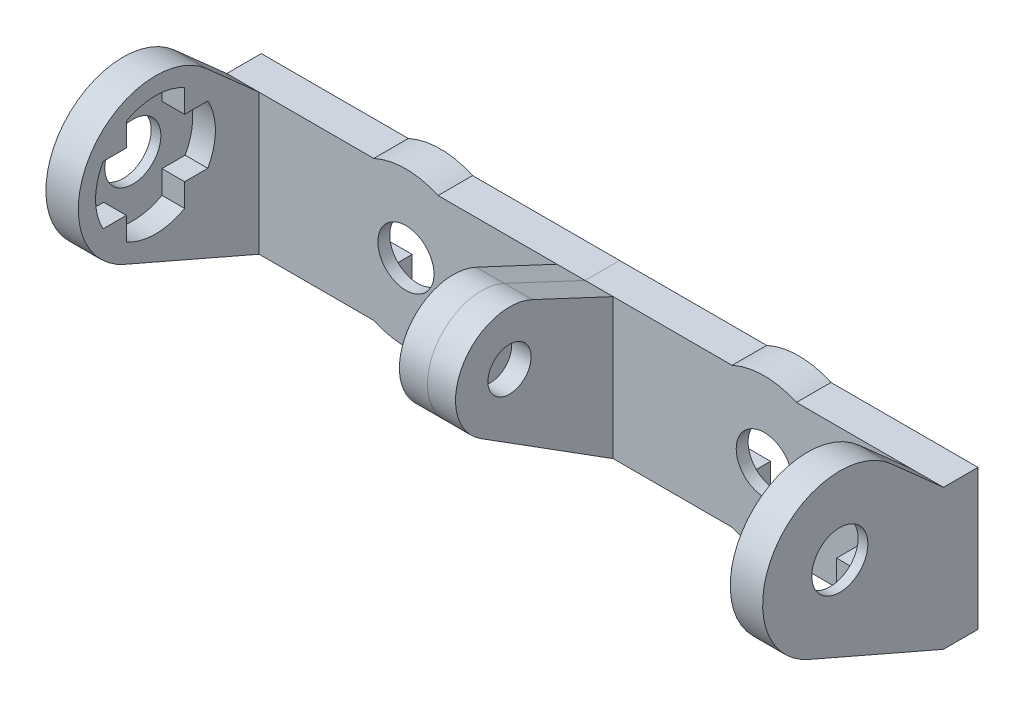
SolidWorks part; units mm, degrees
ref_plane "正面" through (0, 0, 0) normal (0, 0, 1) x (1, 0, 0)
ref_plane "平面" through (0, 0, 0) normal (0, 1, 0) x (1, 0, 0)
ref_plane "右側面" through (0, 0, 0) normal (1, 0, 0) x (0, 0, -1)
sketch "ｽｹｯﾁ1" plane through (0, 0, 0) normal (0, 0, 1) x (1, 0, 0)
  line L0 (0, 0) -> (13.6216, 0)
  line L1 (33.2, 0) -> (33.2, 13.0002)
  line L2 (33.2, 13.0002) -> (19.5784, 13.0002)
  line L3 (0, 13.0002) -> (0, 0)
  line L4 (16.6, 13.0002) -> (16.6, 0) construction
  line L5 (16.6, 6.5001) -> (33.2, 6.5001) construction
  line L6 (13.9218, 11.3099) -> (13.9218, 9.1783) construction
  line L7 (13.9218, 9.1783) -> (11.7902, 9.1783) construction
  line L8 (11.7902, 3.8219) -> (13.9218, 3.8219) construction
  line L9 (13.9218, 3.8219) -> (13.9218, 1.6903) construction
  line L10 (19.2782, 1.6903) -> (19.2782, 3.8219) construction
  line L11 (19.2782, 3.8219) -> (21.4098, 3.8219) construction
  line L12 (21.4098, 9.1783) -> (19.2782, 9.1783) construction
  line L13 (19.2782, 9.1783) -> (19.2782, 11.3099) construction
  line L14 (13.6216, 13.0002) -> (0, 13.0002)
  line L15 (19.5784, 0) -> (33.2, 0)
  arc A0 (19.5784, 13.0002) -> (13.6216, 13.0002) centre (16.6, 6.5001) ccw
  arc A1 (11.7902, 9.1783) -> (11.7902, 3.8219) centre (16.6, 6.5001) ccw construction
  arc A2 (13.9218, 1.6903) -> (19.2782, 1.6903) centre (16.6, 6.5001) ccw construction
  arc A3 (21.4098, 3.8219) -> (21.4098, 9.1783) centre (16.6, 6.5001) ccw construction
  arc A4 (19.2782, 11.3099) -> (13.9218, 11.3099) centre (16.6, 6.5001) ccw construction
  arc A5 (13.6216, 0) -> (19.5784, 0) centre (16.6, 6.5001) ccw
  dimension "D1" = 14.3
extrude "ﾎﾞｽ - 押し出し1" add sketch "ｽｹｯﾁ1" along normal blind 3.2
sketch "ｽｹｯﾁ2" plane through (0, 0, 0) normal (-1, 0, 0) x (0, 0, 1)
  line L3 (3.1997, 0) -> (15.472, 7.7447)
  line L4 (10.6849, 16.502) -> (3.1997, 13.0002)
  line L5 (3.1997, 13.0002) -> (3.1997, 0)
  arc A0 (15.472, 7.7447) -> (10.6849, 16.502) centre (12.8036, 11.9731) ccw
extrude "ﾎﾞｽ - 押し出し2" add sketch "ｽｹｯﾁ2" against normal blind 2.6
sketch "ｽｹｯﾁ3" plane through (33.2, 0, 0) normal (1, 0, 0) x (0, 0, -1)
  line L2 (-3.1997, 13.0002) -> (-8.0519, 17.3157)
  line L3 (-15.6549, 5.4162) -> (-3.1997, 0)
  line L5 (-3.1997, 13.0002) -> (-3.1997, 0)
  arc A0 (-8.0519, 17.3157) -> (-15.6549, 5.4162) centre (-12.8036, 11.9731) ccw
extrude "ﾎﾞｽ - 押し出し3" add sketch "ｽｹｯﾁ3" against normal blind 3
sketch "ｽｹｯﾁ4" plane through (0, 0, 0) normal (0, 0, -1) x (-1, 0, 0)
  line L0 (-19.2232, 11.2775) -> (-19.2232, 9.1233)
  line L1 (-19.2232, 9.1233) -> (-21.3773, 9.1233)
  line L2 (-21.3773, 3.8769) -> (-19.2232, 3.8769)
  line L3 (-19.2232, 3.8769) -> (-19.2232, 1.7228)
  line L4 (-13.9768, 1.7228) -> (-13.9768, 3.8769)
  line L5 (-13.9768, 3.8769) -> (-11.8227, 3.8769)
  line L6 (-19.2782, 11.3099) -> (-19.2782, 9.1783) construction
  line L7 (-19.2782, 9.1783) -> (-21.4098, 9.1783) construction
  line L8 (-21.4098, 3.8219) -> (-19.2782, 3.8219) construction
  line L9 (-19.2782, 3.8219) -> (-19.2782, 1.6903) construction
  line L10 (-13.9218, 1.6903) -> (-13.9218, 3.8219) construction
  line L11 (-13.9218, 3.8219) -> (-11.7902, 3.8219) construction
  line L12 (-11.7902, 9.1783) -> (-13.9218, 9.1783) construction
  line L13 (-13.9218, 9.1783) -> (-13.9218, 11.3099) construction
  line L14 (-11.8227, 9.1233) -> (-13.9768, 9.1233)
  line L15 (-13.9768, 9.1233) -> (-13.9768, 11.2775)
  arc A0 (-21.3773, 9.1233) -> (-21.3773, 3.8769) centre (-16.6, 6.5001) ccw
  arc A1 (-21.4098, 9.1783) -> (-21.4098, 3.8219) centre (-16.6, 6.5001) ccw construction
  arc A2 (-19.2782, 1.6903) -> (-13.9218, 1.6903) centre (-16.6, 6.5001) ccw construction
  arc A3 (-11.7902, 3.8219) -> (-11.7902, 9.1783) centre (-16.6, 6.5001) ccw construction
  arc A4 (-13.9218, 11.3099) -> (-19.2782, 11.3099) centre (-16.6, 6.5001) ccw construction
  arc A5 (-19.2232, 1.7228) -> (-13.9768, 1.7228) centre (-16.6, 6.5001) ccw
  arc A6 (-11.8227, 3.8769) -> (-11.8227, 9.1233) centre (-16.6, 6.5001) ccw
  arc A7 (-13.9768, 11.2775) -> (-19.2232, 11.2775) centre (-16.6, 6.5001) ccw
  dimension "D1" = 5.5051
  dimension "D2" = 0.055
extrude "ｶｯﾄ - 押し出し1" cut sketch "ｽｹｯﾁ4" against normal blind 2.1
sketch "ｽｹｯﾁ5" plane through (0, 0, 2.1) normal (0, 0, -1) x (-1, 0, 0)
  circle A0 centre (-16.6, 6.5001) radius 2.6
  dimension "D1" = 5.2
extrude "ｶｯﾄ - 押し出し2" cut sketch "ｽｹｯﾁ5" against normal up to vertex (1.1 mm away) up to point (30.2, 13.0002, 3.2)
sketch "ｽｹｯﾁ6" plane through (30.2, 0, 0) normal (-1, 0, 0) x (0, 0, 1)
  line L3 (15.5036, 7.1241) -> (15.5036, 9.2731)
  line L4 (15.5036, 9.2731) -> (17.6526, 9.2731)
  line L5 (17.6526, 14.6731) -> (15.5036, 14.6731)
  line L6 (15.5036, 14.6731) -> (15.5036, 16.8221)
  line L7 (10.1036, 16.8221) -> (10.1036, 14.6731)
  line L8 (10.1036, 14.6731) -> (7.9546, 14.6731)
  line L9 (7.9546, 9.2731) -> (10.1036, 9.2731)
  line L10 (10.1036, 9.2731) -> (10.1036, 7.1241)
  arc A1 (17.6526, 9.2731) -> (17.6526, 14.6731) centre (12.8036, 11.9731) ccw
  arc A2 (15.5036, 16.8221) -> (10.1036, 16.8221) centre (12.8036, 11.9731) ccw
  arc A3 (7.9546, 14.6731) -> (7.9546, 9.2731) centre (12.8036, 11.9731) ccw
  arc A4 (10.1036, 7.1241) -> (15.5036, 7.1241) centre (12.8036, 11.9731) ccw
extrude "ｶｯﾄ - 押し出し3" cut sketch "ｽｹｯﾁ6" against normal blind 2.1
sketch "ｽｹｯﾁ7" plane through (32.3, 0, 0) normal (-1, 0, 0) x (0, 0, 1)
  circle A0 centre (12.8036, 11.9731) radius 2.6
  dimension "D1" = 5.2
extrude "ｶｯﾄ - 押し出し4" cut sketch "ｽｹｯﾁ7" against normal up to vertex (0.9 mm away) up to point (33.2, 17.3157, 8.0519)
sketch "ｽｹｯﾁ8" plane through (2.6, 0, 0) normal (1, 0, 0) x (0, 0, -1)
  circle A0 centre (-12.8036, 11.9731) radius 2
  dimension "D1" = 4
extrude "ｶｯﾄ - 押し出し5" cut sketch "ｽｹｯﾁ8" against normal blind 1.8
mirror "ﾐﾗｰ1" about plane through (0, 0, 0) normal (1, 0, 0) of bodies 108
